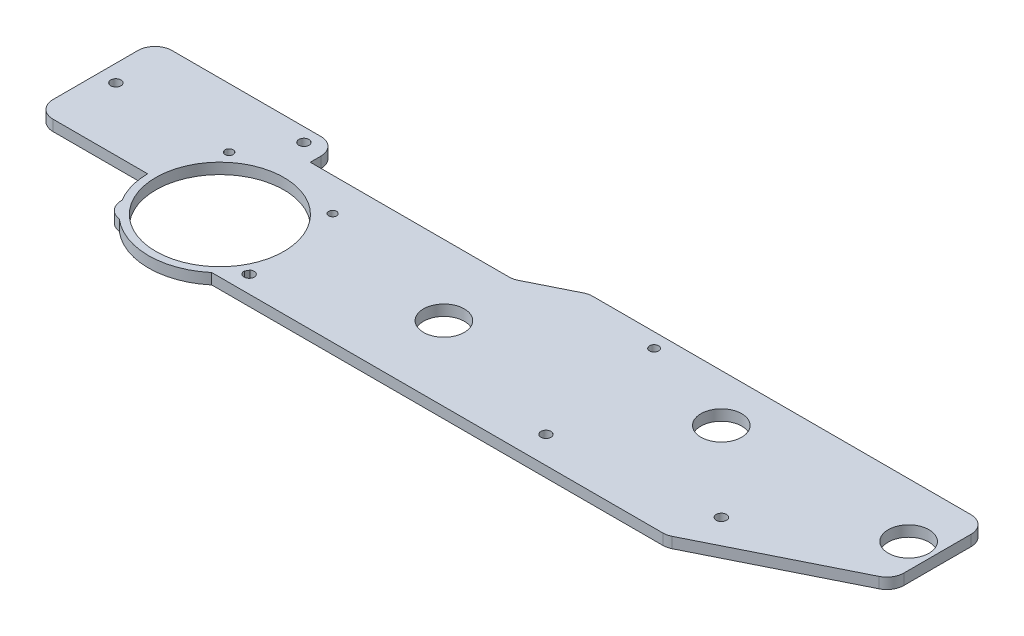
SolidWorks part; units mm, degrees
ref_plane "Front" through (0, 0, 0) normal (0, 0, 1) x (1, 0, 0)
ref_plane "Top" through (0, 0, 0) normal (0, 1, 0) x (1, 0, 0)
ref_plane "Right" through (0, 0, 0) normal (1, 0, 0) x (0, 0, -1)
sketch "Sketch1" plane through (0, 0, 0) normal (0, 1, 0) x (1, 0, 0)
  line L1 (0, 0) -> (210, 0)
  line L2 (0, 0) -> (0, -50)
  line L3 (0, -50) -> (210, -50)
  line L4 (210, 0) -> (210, -50)
  circle A7 centre (3.4895, -16.7877) radius 1.2117
  circle A8 centre (34.3726, -17.194) radius 1.1656
  circle A9 centre (37.5207, -44.9212) radius 1.5
  circle A12 centre (168.9752, -37.4032) radius 1.5173
  circle A13 centre (116, -4.2372) radius 1.3356
  circle A14 centre (12.2576, -3.2748) radius 1.6244
  dimension "D1" = 210
  dimension "D2" = 50
extrude "Boss-Extrude1" add sketch "Sketch1" along normal blind 3.175
sketch "Sketch2" plane through (0, 3.175, 0) normal (0, 1, 0) x (1, 0, 0)
  line L0 (210, 0) -> (0, 0) construction
  line L1 (0, 0) -> (0, -50) construction
  circle A0 centre (10, -26) radius 2
  circle A1 centre (10, -42) radius 2
  circle A2 centre (26, -26) radius 2
  circle A3 centre (26, -42) radius 2
  dimension "D1" = 16
  dimension "D2" = 16
  dimension "D3" = 16
  dimension "D4" = 26
  dimension "D5" = 10
  dimension "D6" = 10
  dimension "D7" = 26
  dimension "D8" = 16
extrude "Cut-Extrude1" cut sketch "Sketch2" against normal blind 10
sketch "Sketch3" plane through (0, 3.175, 0) normal (0, 1, 0) x (1, 0, 0)
  line L0 (210, 0) -> (0, 0) construction
  line L1 (210, 0) -> (0, 0) construction
  circle A0 centre (78.0103, -28.1) radius 6
  circle A1 centre (145.5313, -14) radius 6
  circle A2 centre (18, -34) radius 0.587
  circle A3 centre (26, -26) radius 2 construction
  circle A4 centre (202.6463, -16) radius 6
  dimension "D1" = 28.1
  dimension "D3" = 16
  dimension "D4" = 14
  dimension "D7" = 125.222
  dimension "D2" = 60.2996
  dimension "D5" = 8
  dimension "D6" = 8
  dimension "D8" = 57.15
extrude "Cut-Extrude2" cut sketch "Sketch3" against normal blind 57.15
sketch "Sketch4" [suppressed] plane through (0, 3.175, 0) normal (0, 1, 0) x (1, 0, 0)
  line L0 (3.4895, -16.7877) -> (18, -34)
  line L1 (3.4895, -20.6627) -> (5.9498, -23.5811)
  line L2 (18, -34) -> (34.3726, -17.194)
  line L3 (34.3726, -17.194) -> (75.8499, -28.1)
  line L4 (75.8499, -28.1) -> (37.5207, -44.9212)
  line L5 (7.3432, -17.194) -> (9.8664, -20.303)
  circle A0 centre (18, -34) radius 15.9299
  circle A1 centre (3.4895, -16.7877) radius 3.8751
  circle A2 centre (34.3726, -17.194) radius 3.7227
  circle A3 centre (37.5207, -44.9212) radius 3.8676
  circle A4 centre (75.8499, -28.1) radius 12.797
  circle A5 centre (112.3021, -4.7393) radius 5.1588
  circle A6 centre (118.879, -40.0177) radius 4.9035
  circle A7 centre (140.772, -16) radius 12.6375
  circle A8 centre (168.9752, -37.4032) radius 4.2066
  circle A9 centre (197.922, -16) radius 12.8
sketch "Sketch5" [suppressed] plane through (0, 3.175, 0) normal (0, 1, 0) x (1, 0, 0)
  line L0 (210, 0) -> (0, 0) construction
  line L2 (-0.6266, -16.7877) -> (37.5207, -16.7877)
  line L3 (-0.6266, -16.7877) -> (-0.6266, -44.9212)
  line L4 (-0.6266, -44.9212) -> (37.5207, -44.9212)
  line L5 (37.5207, -16.7877) -> (37.5207, -44.9212)
  line L6 (75.8499, -15.182) -> (37.5207, -15.182)
  line L7 (75.8499, -15.182) -> (75.8499, -44.9212)
  line L8 (75.8499, -44.9212) -> (37.5207, -44.9212)
  line L9 (37.5207, -15.182) -> (37.5207, -44.9212)
  line L10 (112.3021, -4.7393) -> (75.8499, -4.7393)
  line L11 (112.3021, -4.7393) -> (112.3021, -44.9212)
  line L12 (112.3021, -44.9212) -> (75.8499, -44.9212)
  line L13 (75.8499, -4.7393) -> (75.8499, -44.9212)
  line L14 (112.3021, -4.7393) -> (102.3945, -4.7393)
  line L16 (112.3021, -4.7393) -> (112.3021, 0)
  line L17 (112.3021, 0) -> (102.3945, 0)
  line L18 (102.3945, -4.7393) -> (102.3945, 0)
  line L19 (210, -50) -> (210, 0) construction
  line L20 (112.3021, -4.7393) -> (123.1553, -4.7393)
  line L21 (112.3021, -4.7393) -> (112.3021, 0)
  line L22 (112.3021, 0) -> (123.1553, 0)
  line L23 (123.1553, -4.7393) -> (123.1553, 0)
  line L24 (112.3021, -4.7393) -> (140.772, -4.7393)
  line L25 (112.3021, -4.7393) -> (112.3021, -40.0177)
  line L26 (112.3021, -40.0177) -> (140.772, -40.0177)
  line L27 (140.772, -4.7393) -> (140.772, -40.0177)
  line L28 (140.772, -16) -> (168.9752, -16)
  line L29 (140.772, -16) -> (140.772, -40.0177)
  line L30 (140.772, -40.0177) -> (168.9752, -40.0177)
  line L31 (168.9752, -16) -> (168.9752, -40.0177)
  line L32 (168.9752, -4.7393) -> (210, -4.7393)
  line L33 (168.9752, -4.7393) -> (168.9752, -40.0177)
  line L34 (168.9752, -40.0177) -> (210, -40.0177)
  line L35 (210, -4.7393) -> (210, -40.0177)
  line L36 (0, -50) -> (210, -50) construction
  line L37 (160.7629, -40.0177) -> (177.2091, -40.0177)
  line L38 (160.7629, -40.0177) -> (160.7629, -44.9212)
  line L39 (160.7629, -44.9212) -> (177.2091, -44.9212)
  line L40 (177.2091, -40.0177) -> (177.2091, -44.9212)
  line L41 (112.3021, -40.0177) -> (126.3591, -40.0177)
  line L42 (112.3021, -40.0177) -> (112.3021, -47.7828)
  line L43 (112.3021, -47.7828) -> (126.3591, -47.7828)
  line L44 (126.3591, -40.0177) -> (126.3591, -47.7828)
  line L45 (30.5963, -44.9212) -> (44.6115, -44.9212)
  line L46 (30.5963, -44.9212) -> (30.5963, -50)
  line L47 (30.5963, -50) -> (44.6115, -50)
  line L48 (44.6115, -44.9212) -> (44.6115, -50)
  line L50 (-0.6266, -44.9212) -> (30.5963, -44.9212)
  line L51 (-0.6266, -44.9212) -> (-0.6266, -50)
  line L52 (-0.6266, -50) -> (30.5963, -50)
  line L53 (30.5963, -44.9212) -> (30.5963, -50)
  circle A0 centre (3.4895, -16.7877) radius 4.1161
  circle A1 centre (34.3726, -17.194) radius 3.8132
  circle A2 centre (75.8499, -28.1) radius 12.918
  circle A3 centre (112.3021, -4.7393) radius 5.2663
  circle A4 centre (140.772, -16) radius 13.0245
  circle A5 centre (197.922, -16) radius 12.3805
  circle A6 centre (168.9752, -37.4032) radius 4.7643
  circle A7 centre (118.879, -40.0177) radius 5.279
  circle A8 centre (37.5207, -44.9212) radius 4.2049
  line M12 (0, 0) -> (0, -50)
  line M13 (0, -50) -> (210, -50)
  line M14 (210, -50) -> (210, 0)
  line M15 (210, 0) -> (0, 0)
extrude "Cut-Extrude5" [suppressed] cut sketch "Sketch5" against normal blind 11.52 contours A5 L32 L23 L24 A4 L28 L33 M14 M15 | A1 L6 L13 L10 L18 A0 L2 M15 M12 | L8 L48 L34 L40 L39 L38 L30 L26 L44 L43 L42 L12 M13 M14
fillet "Fillet1" [suppressed] radius 5
sketch "Sketch10" plane through (0, 3.175, 0) normal (0, 1, 0) x (1, 0, 0)
  line L0 (210, -27.8594) -> (165.5029, -50)
  line L1 (210, -50) -> (210, 0) construction
  line L2 (0, -50) -> (210, -50) construction
  line L3 (165.5029, -50) -> (210, -50)
  line L4 (210, -50) -> (210, -27.8594)
  line L5 (92.5326, 0) -> (77.6548, -7.4028)
  line L6 (210, 0) -> (0, 0) construction
  line L7 (77.6548, -7.4028) -> (0, -7.4028)
  line L8 (0, 0) -> (0, -50) construction
  line L9 (0, -7.4028) -> (0, 0)
  line L10 (0, 0) -> (92.5326, 0)
extrude "Cut-Extrude7" cut sketch "Sketch10" against normal blind 10
fillet "Fillet3" radius 5 7 edges at (0, 1.5875, 50) (0, 1.5875, 7.4028) (77.6548, 1.5875, 7.4028) (92.5326, 1.5875, 0) (210, 1.5875, 0) (210, 1.5875, 27.8594) (165.5029, 1.5875, 50)
sketch "Sketch11" plane through (0, 3.175, 0) normal (0, 1, 0) x (1, 0, 0)
  circle A0 centre (18, -34) radius 18.5
  circle A1 centre (10, -26) radius 2
  circle A2 centre (10, -42) radius 2
  circle A3 centre (26, -26) radius 2
  circle A4 centre (26, -42) radius 2
extrude "Boss-Extrude4" add sketch "Sketch11" against normal blind 3.175
sketch "Sketch12" plane through (0, 3.175, 0) normal (0, 1, 0) x (1, 0, 0)
  circle A0 centre (18, -34) radius 21
  circle A1 centre (10, -26) radius 2 construction
  circle A2 centre (10, -42) radius 2 construction
  dimension "D1" = 8
  dimension "D2" = 8
extrude "Boss-Extrude5" add sketch "Sketch12" against normal blind 3.175
sketch "Sketch13" plane through (0, 3.175, 0) normal (0, 1, 0) x (1, 0, 0)
  circle A0 centre (18, -34) radius 18.85
extrude "Cut-Extrude8" cut sketch "Sketch13" against normal blind 3.175
sketch "Sketch14" plane through (0, 3.175, 0) normal (0, 1, 0) x (1, 0, 0)
  line L0 (0, -12.4028) -> (0, -23.1833) construction
  line L1 (0, -34.2728) -> (-35.83, -34.2728)
  line L2 (0, -34.2728) -> (0, 0.7272)
  line L3 (0, 0.7272) -> (-35.83, 0.7272)
  line L4 (-35.83, -34.2728) -> (-35.83, 0.7272)
  line L5 (5, -7.4028) -> (76.4796, -7.4028) construction
  line L8 (0, 0.7272) -> (18, 0.7272)
  line L9 (0, 0.7272) -> (0, -12.2485)
  line L10 (0, -12.2485) -> (18, -12.2485)
  line L11 (18, 0.7272) -> (18, -12.2485)
  line M20 (76.4796, -7.4028) -> (5, -7.4028)
  arc M21 (5, -7.4028) -> (0, -12.4028) centre (5, -12.4028) ccw
  line M22 (0, -12.4028) -> (0, -23.1833)
  arc M23 (0, -23.1833) -> (0, -44.8167) centre (18, -34) ccw
  dimension "D4" = 18
  dimension "D1" = 8.13
  dimension "D2" = 35.83
  dimension "D3" = 35
extrude "Boss-Extrude6" add sketch "Sketch14" against normal blind 3.175 contours L4 L1 L2 L3 M23 M22 | L11 L8 L2 L10 M21 M20 region at (-18.2239, 3.175, 16.5271) region at (8.7212, 3.175, 3.5211)
fillet "Fillet4" radius 5 3 edges at (18, 1.5875, -0.7272) (-35.83, 1.5875, 34.2728) (-35.83, 1.5875, -0.7272)
sketch "Sketch15" plane through (0, 3.175, 0) normal (0, 1, 0) x (1, 0, 0)
  line L0 (210, -24.7625) -> (210, -5) construction
  circle A0 centre (122, -42.0581) radius 1.5
  dimension "D1" = 88
extrude "Cut-Extrude9" cut sketch "Sketch15" against normal blind 10
sketch "Sketch16" plane through (0, 3.175, 0) normal (0, 1, 0) x (1, 0, 0)
  line L0 (18, -4.2728) -> (18, -7.4028) construction
  line L1 (13, 0.7272) -> (-30.83, 0.7272) construction
  circle A0 centre (12, -3.2728) radius 1.5
  dimension "D1" = 6
  dimension "D2" = 4
extrude "Cut-Extrude10" cut sketch "Sketch16" against normal blind 10
sketch "Sketch17" plane through (0, 3.175, 0) normal (0, 1, 0) x (1, 0, 0)
  line L0 (13, 0.7272) -> (-30.83, 0.7272) construction
  line L1 (-35.83, -29.2728) -> (-35.83, -4.2728) construction
  circle A0 centre (-30.83, -15.7728) radius 1.5
  dimension "D1" = 16.5
  dimension "D2" = 5
extrude "Cut-Extrude11" cut sketch "Sketch17" against normal blind 10
